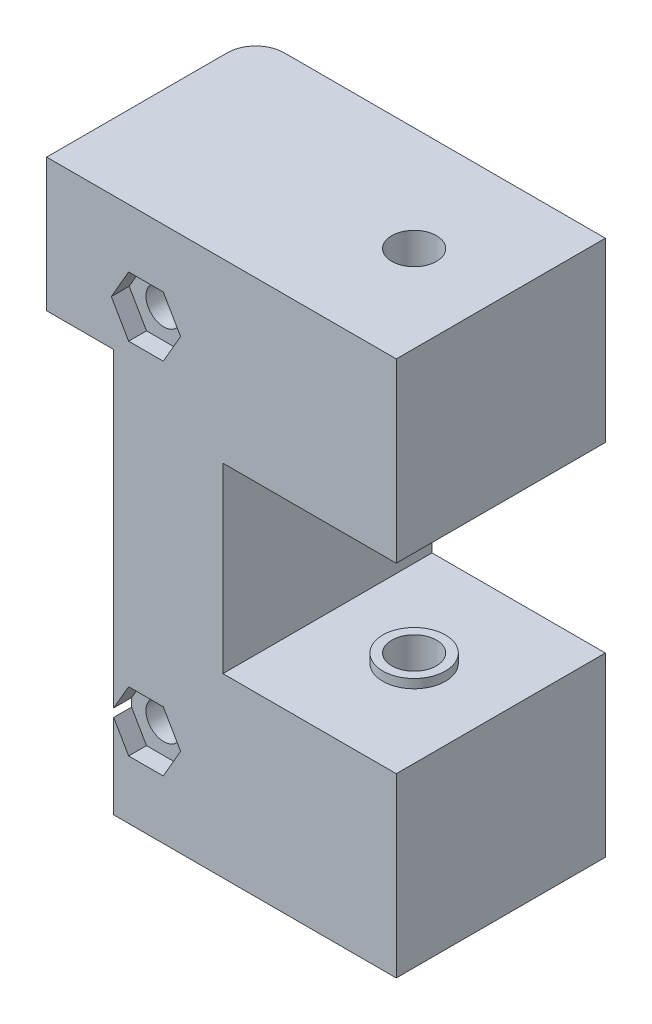
SolidWorks part; units mm, degrees
ref_plane "Front Plane" through (0, 0, 0) normal (0, 0, 1) x (1, 0, 0)
ref_plane "Top Plane" through (0, 0, 0) normal (0, 1, 0) x (1, 0, 0)
ref_plane "Right Plane" through (0, 0, 0) normal (1, 0, 0) x (0, 0, -1)
sketch "MainBlock" plane through (0, 0, 0) normal (0, 0, 1) x (1, 0, 0)
  line L0 (0, 0) -> (39.125, 0)
  line L1 (39.125, 0) -> (39.125, 19.8)
  line L2 (39.125, 19.8) -> (19.725, 19.8)
  line L3 (19.725, 19.8) -> (19.725, 40.2)
  line L4 (19.725, 40.2) -> (39.125, 40.2)
  line L5 (39.125, 40.2) -> (39.125, 60)
  line L6 (39.125, 60) -> (0, 60)
  line L7 (0, 60) -> (0, 0)
  circle A0 centre (11.1125, 50.1) radius 2
  circle A1 centre (11.1125, 9.9) radius 2
  dimension "D4" = 4
  dimension "D1" = 39.125
  dimension "D2" = 60
  dimension "D3" = 20.4
  dimension "D5" = 19.4
  dimension "D6" = 11.1125
  dimension "D7" = 9.9
  dimension "D8" = 9.9
  dimension "D9" = 19.8
  dimension "D10" = 19.8
extrude "MainBlockBoss-Extrude1" add sketch "MainBlock" along normal blind 23.4
sketch "TopHoleCut-Sketch2" plane through (0, 60, 0) normal (0, 1, 0) x (1, 0, 0)
  line L0 (39.125, 0) -> (0, 0) construction
  circle A0 centre (29.425, -11.7) radius 2.5
  dimension "D3" = 5
  dimension "D1" = 11.7
  dimension "D2" = 9.7
extrude "TopHoleCut-Extrude1" cut sketch "TopHoleCut-Sketch2" against normal blind 45
sketch "MountHoleBoreSketch3" plane through (0, 0, 23.4) normal (0, 0, 1) x (1, 0, 0)
  line L1 (14.9875, 50.1) -> (13.05, 53.4558)
  line L2 (13.05, 53.4558) -> (9.175, 53.4558)
  line L3 (9.175, 53.4558) -> (7.2375, 50.1)
  line L4 (7.2375, 50.1) -> (9.175, 46.7442)
  line L5 (9.175, 46.7442) -> (13.05, 46.7442)
  line L6 (13.05, 46.7442) -> (14.9875, 50.1)
  line L7 (14.9875, 9.9) -> (13.05, 13.2558)
  line L8 (13.05, 13.2558) -> (9.175, 13.2558)
  line L9 (9.175, 13.2558) -> (7.2375, 9.9)
  line L10 (7.2375, 9.9) -> (9.175, 6.5442)
  line L11 (9.175, 6.5442) -> (13.05, 6.5442)
  line L12 (13.05, 6.5442) -> (14.9875, 9.9)
  circle A0 centre (11.1125, 50.1) radius 3.3558 construction
  circle A1 centre (11.1125, 9.9) radius 3.3558 construction
  point P10 (11.1125, 53.4558)
  dimension "D1" = 7.75
extrude "MountHoleBoreCut-Extrude2" cut sketch "MountHoleBoreSketch3" against normal blind 2
sketch "TopSpacerSketch4" plane through (0, 40.2, 0) normal (0, -1, 0) x (1, 0, 0)
  circle A0 centre (29.425, 11.7) radius 3.5
  circle A1 centre (29.425, 11.7) radius 2.5
  circle A2 centre (29.425, 11.7) radius 2.5 construction
  dimension "D1" = 7
extrude "TopSpacerBoss-Extrude2" add sketch "TopSpacerSketch4" along normal blind 1
sketch "LowerSpacerSketch5" plane through (0, 19.8, 0) normal (0, 1, 0) x (1, 0, 0)
  circle A0 centre (29.425, -11.7) radius 2.5
  circle A1 centre (29.425, -11.7) radius 2.5 construction
  circle A2 centre (29.425, -11.7) radius 3.5
  circle A3 centre (29.425, -11.7) radius 3.5 construction
extrude "LowerSpacerBoss-Extrude3" add sketch "LowerSpacerSketch5" along normal blind 1
sketch "PushPinHoleSketch1" plane through (0, 0, 0) normal (0, -1, 0) x (1, 0, 0)
  circle A0 centre (29.425, 11.7) radius 1
  circle A1 centre (29.425, 11.7) radius 2.5 construction
  dimension "D1" = 2
extrude "PushPinHoleCut-Extrude1" cut sketch "PushPinHoleSketch1" against normal through all
sketch "MidRailIndentSketch1" plane through (0, 0, 23.4) normal (0, 0, 1) x (1, 0, 0)
  line L0 (0, 60) -> (0, 0) construction
  line L1 (0, 45.1) -> (7.5, 45.1)
  line L2 (0, 45.1) -> (0, 0)
  line L3 (0, 0) -> (7.5, 0)
  line L4 (7.5, 45.1) -> (7.5, 0)
  line L5 (39.125, 60) -> (0, 60) construction
  line L6 (0, 0) -> (39.125, 0) construction
  dimension "D1" = 14.9
  dimension "D3" = 7.5
extrude "MidRailIndentCut-Extrude1" cut sketch "MidRailIndentSketch1" against normal through all
fillet "VerticalSupportFillet1" radius 3.175 1 edges at (0, 52.55, 0)
equation "\"BeltTensionerWidth\"= \"MidRailToAlignWithGantryBlock\" + \"BeltTensionerInnerWidth\" / 2 + \"RailThickness\""
equation "\"BeltTensionerHeight\"= 60mm"
equation "\"BeltTensionerDepth\"= \"BeltTensionerBackWallThickness\" + \"BeltTensionerInnerDepth\"'Equals 23.4"
equation "\"BeltTensionerInnerWidth\"= \"20TGT2PulleyDiameter\" + \"BeltTensionerSpaceBetweenPulleyAndWall\""
equation "\"BeltTensionerInnerHeight\"= \"20TGT2PulleyWidth\" * 2 + \"1mmSpacer\" * 3"
equation "\"BeltTensionerBackWallThickness\"= 4mm"
equation "\"BeltTensionerInnerDepth\"= \"20TGT2PulleyDiameter\" + \"BeltTensionerSpaceBetweenPulleyAndWall\""
equation "\"RailThickness\"= .125in'Spec"
equation "\"HoleOffsetFromEdge\"= \"RailThickness\" * 2.5"
equation "\"LinearGBWithRailDepth\"= 12.75mm'Spec"
equation "\"GABDistanceFromBackToFirstPulley\"= 13.5mm"
equation "\"MidRailToAlignWithGantryBlock\"= \"LinearGBWithRailDepth\" + \"GABDistanceFromBackToFirstPulley\"'All outside cogs must align"
equation "\"20TGT2PulleyDiameter\"= 17.9mm'Spec"
equation "\"BeltTensionerSpaceBetweenPulleyAndWall\"= 1.5mm"
equation "\"BeltTensionerMountingHoleDiameter\"= 4.0mm"
equation "\"BeltTensionerMountingHoleOffsetFromTopOrBottom\"= ( \"BeltTensionerHeight\" - \"BeltTensionerInnerHeight\" ) / 4"
equation "\"20TGT2PulleyWidth\"= 8.7mm'The STL of the Pulley in the diagram is a bit larger"
equation "\"1mmSpacer\"= 1mm"
equation "\"SteelShaft5mmHoleDiameter\"= 5mm"
equation "\"BeltTensionerMountingHoleOuterBoreDepth\"= 2mm"
equation "\"BeltTensionerMountingHoleOuterBoreDiameter\"= 7.75mm"
equation "\"7mmx1mmSpacerDiameter\"= 7mm"
equation "\"7mmx1mmSpacerHeight\"= 1mm"
equation "\"D1@MainBlock\" = \"BeltTensionerWidth\""
equation "\"D4@MainBlock\" = \"BeltTensionerMountingHoleDiameter\""
equation "\"D5@MainBlock\" = \"BeltTensionerInnerWidth\""
equation "\"D6@MainBlock\"=\"HoleOffsetFromEdge\" + \"RailThickness\""
equation "\"D7@MainBlock\"=\"BeltTensionerMountingHoleOffsetFromTopOrBottom\""
equation "\"D8@MainBlock\"=\"BeltTensionerMountingHoleOffsetFromTopOrBottom\""
equation "\"D1@MainBlockBoss-Extrude1\" = \"BeltTensionerDepth\""
equation "\"D1@TopHoleCut-Sketch2\" = \"BeltTensionerDepth\" / 2"
equation "\"D3@TopHoleCut-Sketch2\" = \"SteelShaft5mmHoleDiameter\""
equation "\"D1@MountHoleBoreSketch3\" = \"BeltTensionerMountingHoleOuterBoreDiameter\""
equation "\"D1@MountHoleBoreCut-Extrude2\"=\"BeltTensionerMountingHoleOuterBoreDepth\""
equation "\"D1@TopSpacerSketch4\" = \"7mmx1mmSpacerDiameter\""
equation "\"D1@TopSpacerBoss-Extrude2\" = \"7mmx1mmSpacerHeight\""
equation "\"D1@LowerSpacerBoss-Extrude3\" = \"7mmx1mmSpacerHeight\""
equation "\"SteelPinPushHoleDiameter\"= 2mm"
equation "\"D1@PushPinHoleSketch1\" = \"SteelPinPushHoleDiameter\""
equation "\"BeltTensionerSteelShaftHoleDepthFromTop\"= ( \"SteelShaftLength\" - \"BeltTensionerInnerHeight\" ) / 2 + ( \"BeltTensionerHeight\" - \"BeltTensionerInnerHeight\" ) / 2 + \"BeltTensionerInnerHeight\"'Equals 45"
equation "\"SteelShaftLength\"= 30mm"
equation "\"D1@TopHoleCut-Extrude1\"=\"BeltTensionerSteelShaftHoleDepthFromTop\""
equation "\"D2@TopHoleCut-Sketch2\"=\"BeltTensionerWidth\" -\"MidRailToAlignWithGantryBlock\" - \"RailThickness\""
equation "\"D1@MidRailIndentSketch1\"=\"DistanceAboveMidSideRailToBeltTensioner\""
equation "\"LinearRailWidth\"= 12mm'Spec"
equation "\"MidSideRailVerticalOffset\"= \"LinearRailWidth\" + 3mm'Allows space for RodStabilizer to attach to bottom of MidSideRail"
equation "\"DistanceAboveMidSideRailToBeltTensioner\"= \"VS ToTopOfBeltTensionerAlignedWithYAxisGantryBlockUpperPulley\" - \"V8 ToTopOfMidSideRail\"'Equals 14.9"
equation "\"DistanceFromBeltTensionerTopPulleyToBeltTensionerTop\"= \"7mmx1mmSpacerHeight\" + \"BeltTensionerTopHeight\"'Equals 20.8"
equation "\"BeltTensionerTopHeight\"= ( \"BeltTensionerHeight\" - \"BeltTensionerInnerHeight\" ) / 2'Equals 19.8"
equation "\"GABUpperHeight\"= 4mm"
equation "\"D9@MainBlock\"=\"BeltTensionerTopHeight\""
equation "\"D3@MainBlock\"=\"BeltTensionerInnerHeight\""
equation "\"D2@MainBlock\"=\"BeltTensionerHeight\""
equation "\"LegHeight\"= 70mm'Space needed for PSU/Stepper/Electronics"
equation "\"V1 BottomOfLowerRail\"= \"LegHeight\""
equation "\"LowerEnclosureThickness\"= 5mm"
equation "\"StepperShaftLength\"= 24mm'Pulley will be attached to the end"
equation "\"ZAxisLeadScrewLength\"= 200mm"
equation "\"LM8UUHeight\"= 24mm'Spec"
equation "\"V2 ToBedAtTopOfZAxis\"= \"V1 BottomOfLowerRail\" - \"LowerEnclosureThickness\" + \"StepperShaftLength\" + \"ZAxisLeadScrewLength\" - \"LM8UUHeight\" / 2'Equals 277"
equation "\"BedToBuildPlateStandoffLength\"= 15mm"
equation "\"BuildPlateHeight\"= 8mm'Spec"
equation "\"V4 ToTopOfBuildPlate/HotEndTip\"= \"V2 ToBedAtTopOfZAxis\" + \"BedToBuildPlateStandoffLength\" + \"BuildPlateHeight\""
equation "\"HotEndToTopOfXAxisGB\"= 71.68487mm'Equals 71.68487. Measured after installed onto X-Axis linear rail guide block"
equation "\"LinearGBWidth\"= 27mm'Spec"
equation "\"TopOfGBToBottomOfLinearRail\"= \"LinearGBWidth\" / 2 + \"LinearRailWidth\" / 2'Equals 19.5"
equation "\"V5 ToBottomOfXAxisLinearRail\"= \"V4 ToTopOfBuildPlate/HotEndTip\" + \"HotEndToTopOfXAxisGB\" - \"TopOfGBToBottomOfLinearRail\"'Equals 352.18487"
equation "\"GABMidWallHeight\"= 28mm'Must equal 28 or changes alignment"
equation "\"GABLowerHeight\"= 4mm"
equation "\"GABHeight\"= \"GABLowerHeight\" + \"GABMidWallHeight\" + \"GABUpperHeight\""
equation "\"V6 ToMiddleOfYAxisGantryBlock\"= \"V5 ToBottomOfXAxisLinearRail\" - \"GABHeight\" / 2'Equals 334.18487"
equation "\"V8 ToTopOfMidSideRail\"= \"V6 ToMiddleOfYAxisGantryBlock\" + \"MidSideRailVerticalOffset\"'Equals 349.18487"
equation "\"VS ToTopOfBeltTensionerAlignedWithYAxisGantryBlockUpperPulley\"= \"V5 ToBottomOfXAxisLinearRail\" - \"DistanceFromXAxisLinearRailBottomAndTopOfGantryPulley\" + \"DistanceFromBeltTensionerTopPulleyToBeltTensionerTop\"'Equals 364.08487"
equation "\"DistanceFromXAxisLinearRailBottomAndTopOfGantryPulley\"= \"GABUpperHeight\" + \"GABMidShortRiserHeight\" - \"GABRiserBossOffset\"'Equals 8.9"
equation "\"GABMidShortRiserHeight\"= \"GABMidWallHeight\" / 2 - \"20TGT2PulleyWidth\"'Equals 5.3"
equation "\"GABRiserBossOffset\"= 0.4mm'Aligns Pulleys inside edges to be 2.5mm (.5mm apart top to bottom)"
equation "\"D1@VerticalSupportFillet1\"=\"RailThickness\""
